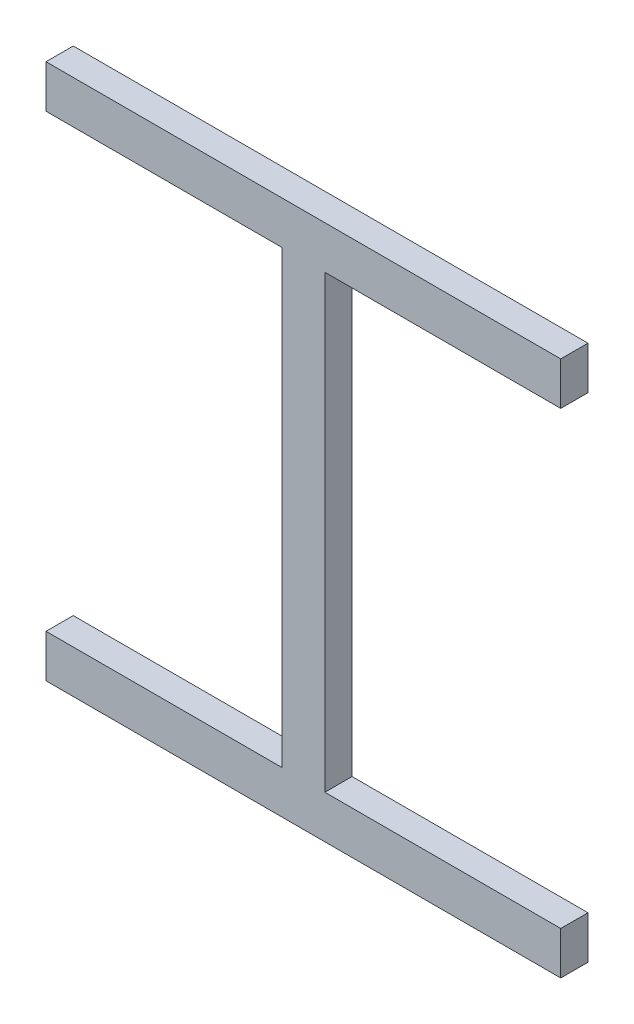
SolidWorks part; units mm, degrees
ref_plane "Front Plane" through (0, 0, 0) normal (0, 0, 1) x (1, 0, 0)
ref_plane "Top Plane" through (0, 0, 0) normal (0, 1, 0) x (1, 0, 0)
ref_plane "Right Plane" through (0, 0, 0) normal (1, 0, 0) x (0, 0, -1)
sketch "Sketch1" plane through (0, 0, 0) normal (0, 0, 1) x (1, 0, 0)
  line L0 (-240, -210) -> (-240, -250)
  line L1 (-240, 250) -> (240, 250)
  line L2 (-240, 250) -> (-240, 210)
  line L3 (-240, -250) -> (240, -250)
  line L4 (0, 250) -> (0, -250) construction
  line L5 (-240, 210) -> (-20, 210)
  line L6 (240, -210) -> (240, -250)
  line L7 (-240, -210) -> (-20, -210)
  line L8 (-20, 210) -> (-20, -210)
  line L9 (240, -210) -> (20, -210)
  line L10 (20, 210) -> (20, -210)
  line L11 (240, 210) -> (20, 210)
  line L12 (240, 250) -> (240, 210)
  dimension "Width" = 480
  dimension "Depth" = 500
  dimension "Web_thickness" = 40
  dimension "Thickness" = 40
extrude "BaseSection" add sketch "Sketch1" along normal mid plane 25.4
